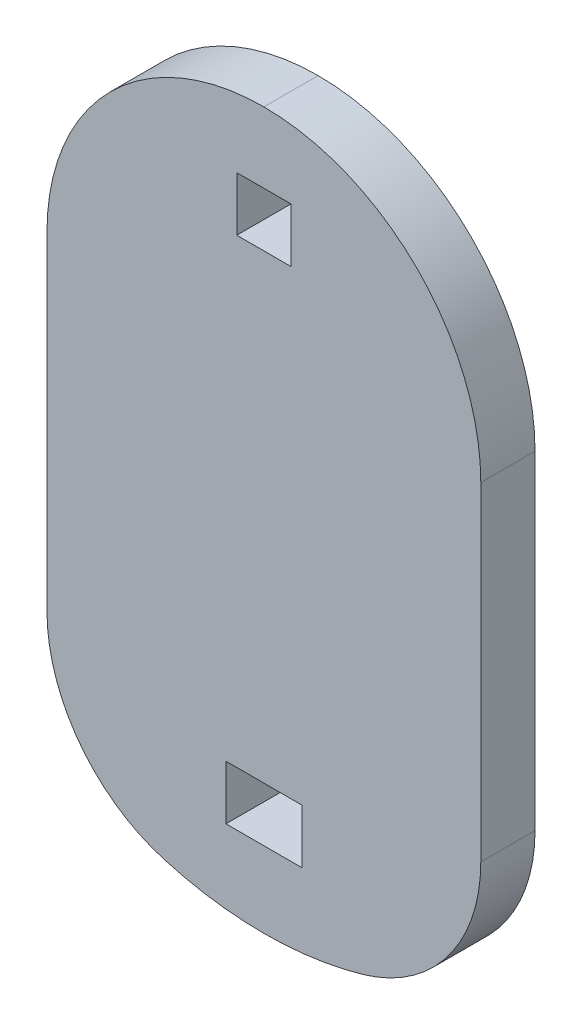
SolidWorks part; units mm, degrees
material "Acrylic (Medium-high impact)"
ref_plane "Front Plane" through (0, 0, 0) normal (0, 0, 1) x (1, 0, 0)
ref_plane "Top Plane" through (0, 0, 0) normal (0, 1, 0) x (1, 0, 0)
ref_plane "Right Plane" through (0, 0, 0) normal (1, 0, 0) x (0, 0, -1)
sketch "Sketch1" plane through (0, 0, 0) normal (0, 0, 1) x (1, 0, 0)
  circle A0 centre (0, 0) radius 33
  dimension "D1" = 66
extrude "Boss-Extrude1" add sketch "Sketch1" along normal blind 5
sketch "Sketch6" plane through (0, 0, 5) normal (0, 0, 1) x (1, 0, 0)
  line L0 (-20, 26.2488) -> (-20, -26.2488)
  line L1 (20, -26.2488) -> (20, 26.2488)
  arc A0 (20, -26.2488) -> (20, 26.2488) centre (0, 0) ccw
  circle A1 centre (0, 0) radius 33
  arc A2 (-20, 26.2488) -> (-20, -26.2488) centre (0, 0) ccw
  dimension "D2" = 20
  dimension "D3" = 40
  dimension "D1" = 0
extrude "Cut-Extrude3" cut sketch "Sketch6" against normal blind 10
fillet "Fillet2" radius 20 2 edges at (-20, 26.2488, 2.5) (20, 26.2488, 2.5)
fillet "Fillet3" radius 15 2 edges at (20, -26.2488, 2.5) (-20, -26.2488, 2.5)
sketch "Sketch7" plane through (0, 0, 5) normal (0, 0, 1) x (1, 0, 0)
  line L1 (-2.5, 26.5) -> (2.5, 26.5)
  line L2 (-2.5, 26.5) -> (-2.5, 21.5)
  line L3 (-2.5, 21.5) -> (2.5, 21.5)
  line L4 (2.5, 26.5) -> (2.5, 21.5)
  line L5 (-3.5, -21) -> (3.5, -21)
  line L6 (-3.5, -21) -> (-3.5, -26)
  line L7 (-3.5, -26) -> (3.5, -26)
  line L8 (3.5, -21) -> (3.5, -26)
  point P9 (0, 21.5)
  point P11 (0, -21)
  dimension "D1" = 6.5
  dimension "D2" = 42.5
  dimension "D3" = 5
  dimension "D4" = 5
  dimension "D5" = 7
extrude "Cut-Extrude4" cut sketch "Sketch7" against normal blind 10
sketch "Sketch2" plane through (0, 0, 5) normal (0, 0, 1) x (1, 0, 0)
  line L1 (-5, 26.5) -> (5, 26.5)
  line L2 (-5, 26.5) -> (-5, 21.5)
  line L3 (-5, 21.5) -> (5, 21.5)
  line L4 (5, 26.5) -> (5, 21.5)
  line L5 (-5, 26.5) -> (5, 21.5) construction
  line L6 (-5, 21.5) -> (5, 26.5) construction
  point P0 (0, 24)
  dimension "D1" = 5
  dimension "D2" = 26.5
  dimension "D3" = 10
extrude "Boss-Extrude2" [suppressed] add sketch "Sketch2" along normal blind 38
sketch "Sketch3" [suppressed] plane through (0, 26.5, 0) normal (0, 1, 0) x (1, 0, 0)
  line L0 (5, -5) -> (-5, -5) construction
  line L1 (5, -43) -> (-5, -43) construction
  circle A0 centre (0, -12) radius 0.5
  circle A1 centre (0, -14) radius 0.5
  circle A2 centre (0, -16) radius 0.5
  circle A3 centre (0, -18) radius 0.5
  circle A4 centre (0, -20) radius 0.5
  circle A5 centre (0, -22) radius 0.5
  circle A6 centre (0, -40.5) radius 0.5
  circle A7 centre (0, -38.5) radius 0.5
  circle A8 centre (0, -36.5) radius 0.5
  circle A9 centre (0, -34.5) radius 0.5
  circle A10 centre (0, -32.5) radius 0.5
  circle A11 centre (0, -30.5) radius 0.5
  point P20 (0, -43)
  dimension "D2" = 1
  dimension "D5" = 8.5
  dimension "D6" = 2
  dimension "D1" = 7
  dimension "D7" = 2
  dimension "D3" = 6
  dimension "D4" = 6
extrude "Cut-Extrude1" [suppressed] cut sketch "Sketch3" against normal blind 5
sketch "Sketch4" [suppressed] plane through (0, 0, 5) normal (0, 0, 1) x (1, 0, 0)
  line L1 (-7.5, -20.5) -> (7.5, -20.5)
  line L2 (-7.5, -20.5) -> (-7.5, -25.5)
  line L3 (-7.5, -25.5) -> (7.5, -25.5)
  line L4 (7.5, -20.5) -> (7.5, -25.5)
  line L5 (-7.5, -20.5) -> (7.5, -25.5) construction
  line L6 (-7.5, -25.5) -> (7.5, -20.5) construction
  line L7 (-5, 21.5) -> (5, 21.5) construction
  point P0 (0, -23)
  dimension "D1" = 42
  dimension "D2" = 15
  dimension "D3" = 5
extrude "Boss-Extrude3" [suppressed] add sketch "Sketch4" along normal blind 32
sketch "Sketch5" [suppressed] plane through (0, -20.5, 0) normal (0, 1, 0) x (1, 0, 0)
  line L0 (-7.5, -5) -> (-3.5, -5) construction
  circle A0 centre (0, -26.25) radius 3.8
  dimension "D1" = 21.25
  dimension "D2" = 7.6
extrude "Cut-Extrude2" [suppressed] cut sketch "Sketch5" against normal blind 28
fillet "Fillet4" [suppressed] radius 0.5
